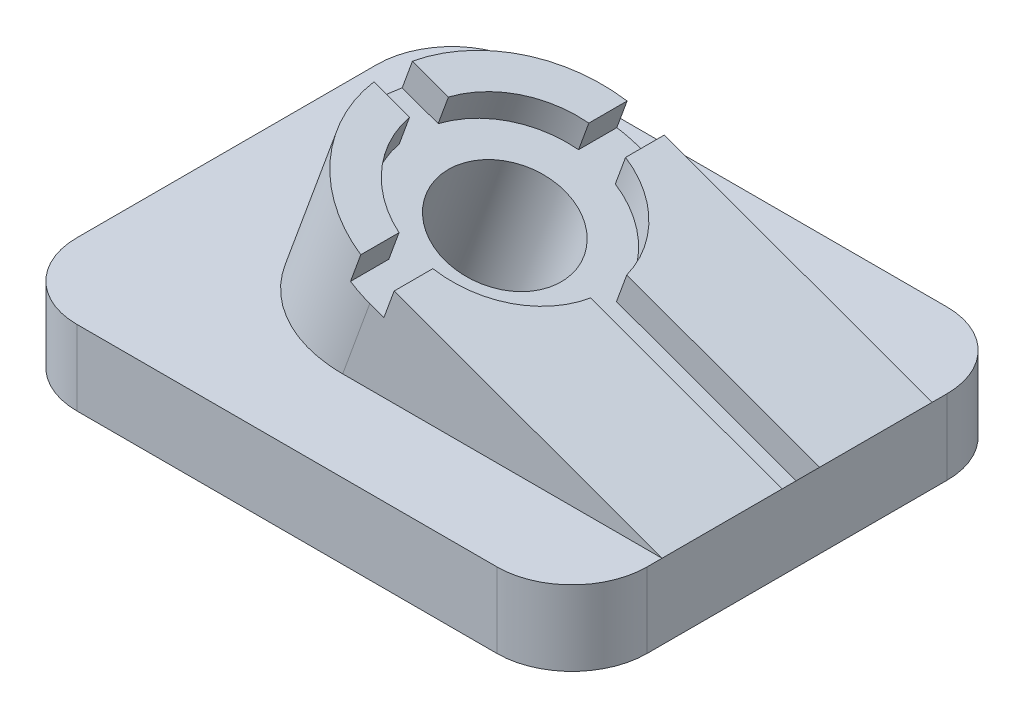
SolidWorks part; units mm, degrees
material "Nickel"
ref_plane "Front Plane" through (0, 0, 0) normal (0, 0, 1) x (1, 0, 0)
ref_plane "Top Plane" through (0, 0, 0) normal (0, 1, 0) x (1, 0, 0)
ref_plane "Right Plane" through (0, 0, 0) normal (1, 0, 0) x (0, 0, -1)
sketch "Sketch1" plane through (0, 0, 0) normal (0, 0, 1) x (1, 0, 0)
  line L0 (-55.4248, 0) -> (55.4248, 0) construction
  line L1 (0, 43.8816) -> (0, -43.8816) construction
  line L2 (-38, 5) -> (38, 5)
  line L3 (38, 5) -> (38, -5)
  line L4 (38, -5) -> (-38, -5)
  line L5 (-38, -5) -> (-38, 5)
  line L6 (38, 5) -> (-16.5022, 24.8372)
  line L7 (-16.5022, 24.8372) -> (-23.7223, 5)
  point P3 (0, 0)
  point P6 (0, 0)
  dimension "D1" = 76
  dimension "D2" = 10
  dimension "D3" = 20
  dimension "D4" = 58
extrude "Boss-Extrude1" add sketch "Sketch1" along normal mid plane 60 contours L5 L4 L3 L2 region at (0, 0, 0)
extrude "Boss-Extrude2" add sketch "Sketch1<4>" along normal mid plane 36 contours L6 L7 L2 region at (-0.7415, 11.6124, 0)
sketch "Sketch1<4>" plane through (0, 0, 0) normal (0, 0, 1) x (1, 0, 0) same geometry as "Sketch1"
sketch "Sketch2" plane through (6.0521, 16.6281, 0) normal (0.342, 0.9397, 0) x (0.9397, -0.342, 0)
  line L0 (-6.0018, 18) -> (-6.0018, -18) construction
  line L1 (-29.0152, 0) -> (17.0116, 0) construction
  line L2 (33.9982, -18) -> (33.9982, 18) construction
  line L4 (-24.0018, 18) -> (-24.0018, -18)
  line L5 (-24.0018, -18) -> (-6.0018, -18)
  line L6 (-24.0018, 18) -> (-6.0018, 18)
  line L7 (33.9982, 3) -> (6.6473, 3)
  line L8 (33.9982, -2) -> (6.8435, -2)
  line L9 (-18.6509, 3) -> (-23.75, 3)
  line L10 (-18.847, -2) -> (-23.8903, -2)
  line L11 (-4.0018, -18) -> (-4.0018, -12.8452)
  line L12 (33.9982, -18) -> (-24.0018, -18) construction
  line L13 (-9.0018, -17.7482) -> (-9.0018, -12.6491)
  line L14 (-9.0018, 12.6491) -> (-9.0018, 17.7482)
  line L15 (-4.0018, 12.8452) -> (-4.0018, 18)
  line L16 (33.9982, 18) -> (-24.0018, 18) construction
  arc A0 (-6.0018, 18) -> (-6.0018, -18) centre (-6.0018, 0) ccw
  circle A1 centre (-6.0018, 0) radius 8
  arc A2 (6.6473, 3) -> (-4.0018, 12.8452) centre (-6.0018, 0) ccw
  arc A3 (-9.0018, 12.6491) -> (-18.6509, 3) centre (-6.0018, 0) ccw
  arc A4 (-18.847, -2) -> (-9.0018, -12.6491) centre (-6.0018, 0) ccw
  arc A5 (-4.0018, -12.8452) -> (6.8435, -2) centre (-6.0018, 0) ccw
  point P5 (-6.0018, 0)
  point P8 (-6.0018, 0)
  line M8 (33.9982, 18) -> (-24.0018, 18)
  line M9 (-24.0018, 18) -> (-24.0018, -18)
  line M10 (-24.0018, -18) -> (33.9982, -18)
  line M11 (33.9982, -18) -> (33.9982, 18)
  dimension "D2" = 18
  dimension "D3" = 16
  dimension "D4" = 26
  dimension "D1" = 40
  dimension "D5" = 3
  dimension "D6" = 5
  dimension "D7" = 3
  dimension "D8" = 5
extrude "Cut-Extrude1" cut sketch "Sketch2" against normal up to surface (21.1103 mm away) contours A0 M8 M9 | A0 L4 M10 region at (-12.724, 23.462, -13.9794) region at (-12.724, 23.462, 13.9794) up to face at (3.5694, 5, 0)
extrude "Cut-Extrude2" cut sketch "Sketch12<4>" against normal through all contours A1 region at (0.4123, 18.6808, 0)
sketch "Sketch12<4>" plane through (6.0521, 16.6281, 0) normal (0.342, 0.9397, 0) x (0.9397, -0.342, 0) same geometry as "Sketch2"
extrude "Cut-Extrude3" cut sketch "Sketch12<5>" against normal blind 4 contours L11 A5 L8 L7 A2 L15 A0 L14 A3 L9 L10 A4 L13 A1 M11 M8 M10 region at (-15.8037, 24.5829, -1.4482)
sketch "Sketch12<5>" plane through (6.0521, 16.6281, 0) normal (0.342, 0.9397, 0) x (0.9397, -0.342, 0) same geometry as "Sketch2"
fillet "Fillet1" radius 10 4 edges at (-38, 0, -30) (38, 0, -30) (38, 0, 30) (-38, 0, 30)
